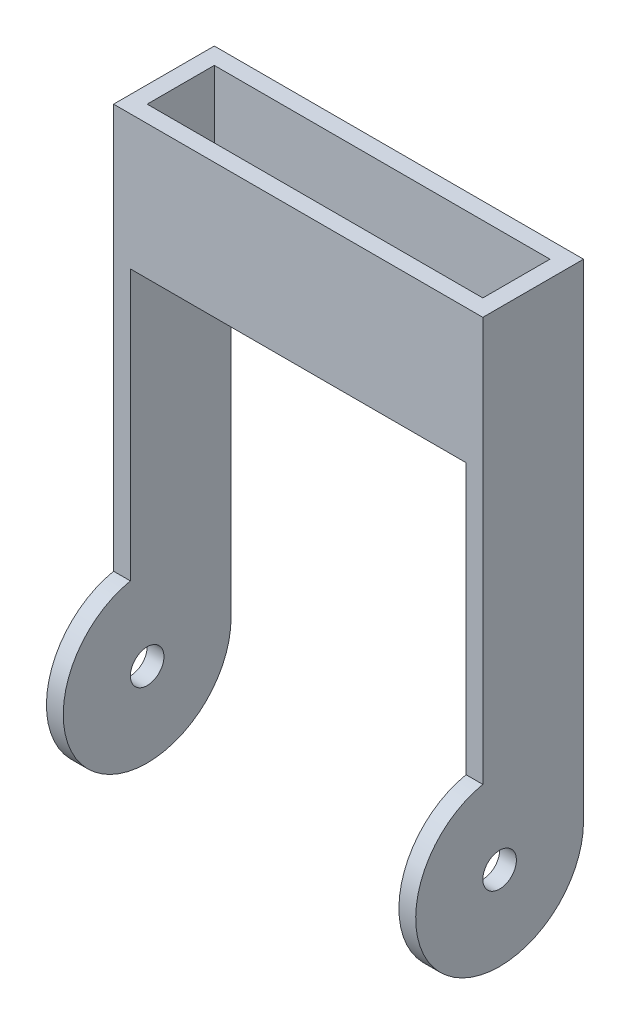
SolidWorks part; units mm, degrees
material "ABS"
ref_plane "Front Plane" through (0, 0, 0) normal (0, 0, 1) x (1, 0, 0)
ref_plane "Top Plane" through (0, 0, 0) normal (0, 1, 0) x (1, 0, 0)
ref_plane "Right Plane" through (0, 0, 0) normal (1, 0, 0) x (0, 0, -1)
sketch "ProbeProfile" plane through (0, 0, 0) normal (0, 1, 0) x (1, 0, 0)
  line L1 (-31.75, -6.35) -> (31.75, -6.35)
  line L2 (-31.75, -6.35) -> (-31.75, 6.35)
  line L3 (-31.75, 6.35) -> (31.75, 6.35)
  line L4 (31.75, -6.35) -> (31.75, 6.35)
  line L5 (-31.75, -6.35) -> (31.75, 6.35) construction
  line L6 (-31.75, 6.35) -> (31.75, -6.35) construction
  point P0 (0, 0)
  dimension "D1" = 12.7
  dimension "D2" = 63.5
extrude "Extrude-Thin1" add sketch "ProbeProfile" along normal blind 25.4 thin thin type one direction wall 3.175
sketch "Sketch2" plane through (0, 0, 0) normal (1, 0, 0) x (0, 0, -1)
  line L1 (9.525, 25.4) -> (9.525, 0) construction
  line L2 (9.525, 0) -> (-9.525, 0) construction
  circle A0 centre (-6.35, -66.675) radius 15.875
  point P4 (9.525, -66.675)
  dimension "D1" = 31.75
  dimension "D2" = 66.675
extrude "Boss-Extrude1" add sketch "Sketch2" along normal mid plane 69.85 separate body
extrude "Cut-Extrude1" cut sketch "Sketch2<2>" against normal mid plane 63.5
sketch "Sketch2<2>" plane through (0, 0, 0) normal (1, 0, 0) x (0, 0, -1) same geometry as "Sketch2"
sketch "Sketch3" plane through (0, 0, 0) normal (0, -1, 0) x (1, 0, 0)
  line L0 (-34.925, 9.525) -> (34.925, 9.525) construction
  line L1 (34.925, -9.525) -> (31.75, -9.525)
  line L2 (34.925, -9.525) -> (34.925, 9.525)
  line L3 (34.925, 9.525) -> (31.75, 9.525)
  line L4 (31.75, -9.525) -> (31.75, 9.525)
  line L5 (-31.75, -6.35) -> (-31.75, 6.35) construction
  line L6 (-34.925, -9.525) -> (-31.75, -9.525)
  line L7 (-34.925, -9.525) -> (-34.925, 9.525)
  line L8 (-34.925, 9.525) -> (-31.75, 9.525)
  line L9 (-31.75, -9.525) -> (-31.75, 9.525)
  line L10 (31.75, 6.35) -> (31.75, -6.35) construction
extrude "Boss-Extrude2" add sketch "Sketch3" along normal up to surface (66.675 mm away) up to face at (-34.925, -66.675, -9.525)
sketch "Sketch4" plane through (-34.925, 0, 0) normal (-1, 0, 0) x (0, 0, 1)
  circle A0 centre (6.35, -66.675) radius 3.175
  point P0 (6.35, -66.675)
  dimension "D1" = 6.35
extrude "Cut-Extrude2" cut sketch "Sketch4" against normal up to surface (69.85 mm away)
